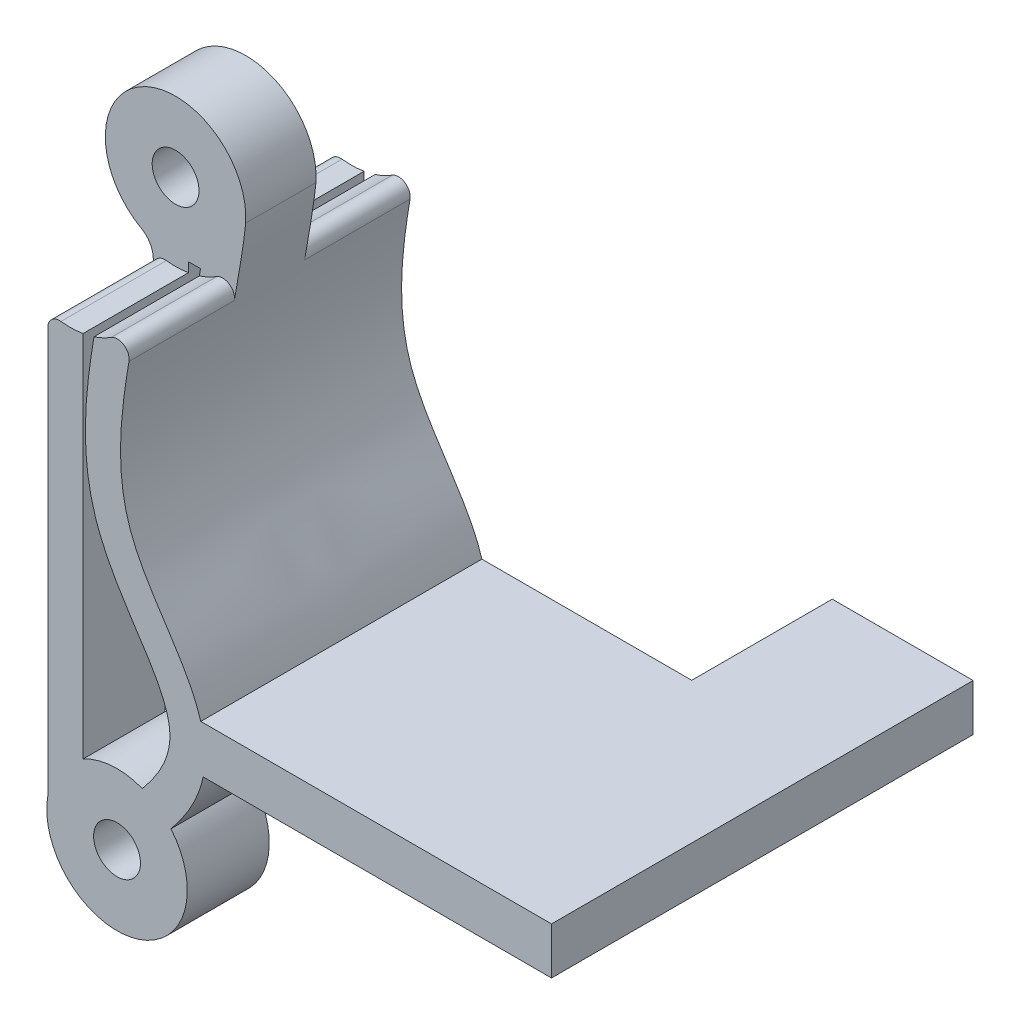
SolidWorks part; units mm, degrees
ref_plane "Front Plane" through (0, 0, 0) normal (0, 0, 1) x (1, 0, 0)
ref_plane "Top Plane" through (0, 0, 0) normal (0, 1, 0) x (1, 0, 0)
ref_plane "Right Plane" through (0, 0, 0) normal (1, 0, 0) x (0, 0, -1)
sketch "Sketch1" plane through (0, 0, 0) normal (0, 0, 1) x (1, 0, 0)
  line L3 (0.9027, 23.1193) -> (0.9027, 44.7293) construction
  line L4 (0.9027, 44.7293) -> (-1.0973, 44.7293) construction
  line L5 (-2.0488, 41.8842) -> (-2.0488, 23.6567)
  line L6 (-0.0313, 41.8842) -> (-0.5488, 41.8842)
  line L7 (-0.5488, 41.8842) -> (-0.5488, 25.7448)
  line L10 (-0.5488, 43.3332) -> (-0.5488, 23.4977) construction
  line L12 (1003.2054, 25.0421) -> (3.2054, 25.0421) construction
  line L13 (-2.0488, 41.8842) -> (49997.9512, 41.8842) construction
  line L14 (-0.5488, 25.0421) -> (-49996.7946, 25.0421) construction
  arc A0 (-2.0488, 41.8842) -> (1.896, 44.5297) centre (-1.0973, 44.7293) cw
  arc A2 (-2.0488, 23.6567) -> (3.2054, 25.0421) centre (0.9027, 23.1193) ccw
  circle A3 centre (-1.0973, 44.7293) radius 1
  circle A4 centre (0.9027, 23.1193) radius 1
  arc A7 (-0.5488, 23.4977) -> (0.9027, 24.6193) centre (0.9027, 23.1193) ccw construction
  arc A8 (-0.5488, 43.3332) -> (0.4006, 44.6513) centre (-1.0973, 44.7293) cw construction
  arc A9 (1.9829, 25.918) -> (-0.5488, 25.7448) centre (0.9027, 23.1193) ccw
  spline S0 degree 3 poles (1.896, 44.5297) (1.6161, 41.7589) (-0.9369, 33.9552) (6.8447, 29.4175) (3.2054, 25.0421) knots 0 0 0 0 0.461185 1 1 1 1
  spline S1 degree 1 poles (0.4006, 44.6513) (0.9027, 24.6193) knots 0 0 1 1 construction
  spline S2 degree 3 poles (0.4006, 44.6513) (0.3814, 44.4652) (0.3367, 44.1044) (0.2163, 43.3069) (0.0657, 42.4502) (-0.0914, 41.5355) (-0.2432, 40.5851) (-0.402, 39.3533) (-0.4791, 37.8282) (-0.3759, 36.2754) (0.01, 34.6811) (0.9413, 32.7707) (2.0354, 31.2469) (2.8047, 29.9095) (3.1286, 29.0309) (3.1964, 28.2674) (3.0323, 27.5503) (2.6663, 26.8291) (2.3349, 26.3502) (2.1068, 26.0672) (2.0129, 25.9541) (1.9549, 25.8844) (1.8019, 25.7008) (1.4593, 25.2881) (1.1253, 24.887) (0.9027, 24.6193) knots 0.001801 0.001801 0.001801 0.001801 0.034767 0.067734 0.132717 0.165683 0.1996 0.265533 0.331467 0.3974 0.463333 0.529266 0.661132 0.727066 0.792999 0.858932 0.924865 0.957832 0.990798 0.99904 1.001358 1.005479 1.00754 1.023765 1.056732 1.056732 1.056732 1.056732 only from (-0.0313, 41.8842) to (1.9829, 25.918)
  dimension "D1" = 2
  dimension "D2" = 3
  dimension "D3" = 21.61
  dimension "D4" = 2
  dimension "D5" = 1.5
  dimension "D6" = 6
  dimension "D7" = 1.5
extrude "Boss-Extrude1" add sketch "Sketch1" along normal blind 12
ref_plane "midplane" through (0, 0, 6) normal (0, 0, 1) x (1, 0, 0)
sketch "Sketch2" plane through (0, 0, 12) normal (0, 0, 1) x (1, 0, 0)
  circle A4 centre (-1.0973, 44.7293) radius 3.3
  dimension "D1" = 6.6
extrude "Cut-Extrude1" cut sketch "Sketch2" against normal blind 4.5
mirror "Mirror1" about plane through (0, 0, 6) normal (0, 0, 1) of "Cut-Extrude1"
sketch "Sketch3" plane through (0, 0, 6) normal (0, 0, 1) x (1, 0, 0)
  circle A2 centre (0.9027, 23.1193) radius 3.3
  dimension "D1" = 6.6
extrude "Cut-Extrude2" cut sketch "Sketch3" against normal blind 2.5 and the other way blind 2.5
ref_plane "Plane1" through (19.4512, 0, 0) normal (1, 0, 0) x (0, 0, -1)
sketch "Sketch4" plane through (19.4512, 0, 0) normal (1, 0, 0) x (0, 0, -1)
  line L0 (-12, 42.9328) -> (-12, 25.0421) construction
  line L1 (-12, 29.6486) -> (0, 29.6486)
  line L2 (-12, 29.6486) -> (-12, 27.6486)
  line L3 (-12, 27.6486) -> (0, 27.6486)
  line L4 (0, 29.6486) -> (0, 27.6486)
  line L5 (0, 25.0421) -> (0, 42.9328) construction
  dimension "D1" = 2
extrude "Boss-Extrude2" add sketch "Sketch4" against normal up to next
sketch "Sketch5" plane through (0, 0, 0) normal (0, 0, -1) x (-1, 0, 0)
  line L0 (-19.4512, 6.6) -> (-19.4512, -6.6) construction
  line L1 (-19.4512, 29.6486) -> (-13.4372, 29.6486)
  line L2 (-19.4512, 29.6486) -> (-19.4512, 27.6486)
  line L3 (-19.4512, 27.6486) -> (-13.4372, 27.6486)
  line L4 (-13.4372, 29.6486) -> (-13.4372, 27.6486)
  line L5 (-4.5791, 27.6486) -> (-19.4512, 27.6486) construction
  line L6 (-4.4786, 29.6486) -> (-19.4512, 29.6486) construction
extrude "Boss-Extrude3" add sketch "Sketch5" along normal blind 6
fillet "Fillet1" radius 0.5 4 edges at (-2.0488, 41.5694, 2.25) (-2.0488, 41.5694, 9.75) (1.6708, 42.9328, 2.25) (1.6708, 42.9328, 9.75)
fillet "Fillet2" radius 1 1 edges at (-2.0488, 41.8842, 6)
equation "\"axle-diameter\"=2"
equation "\"switch-thickness\"=12"
equation "\"base-width\"=4.0"
equation "\"axle-bushing-radius\"=3"
equation "\"D1@Sketch1\"=\"axle-diameter\""
equation "\"D2@Sketch1\"=\"axle-bushing-radius\""
equation "\"D1@Cut-Extrude1\"=\"switch-thickness\"/3+\"clearance\""
equation "\"D1@Cut-Extrude2\"=\"switch-thickness\"/6+\"clearance\""
equation "\"D2@Cut-Extrude2\"=\"switch-thickness\"/6+\"clearance\""
equation "\"D1@Boss-Extrude1\"=\"switch-thickness\""
equation "\"D1@Sketch2\"=\"axle-bushing-radius\"*2.2"
equation "\"D1@Sketch3\"=\"axle-bushing-radius\"*2.2"
equation "\"clearance\"= 0.5"
